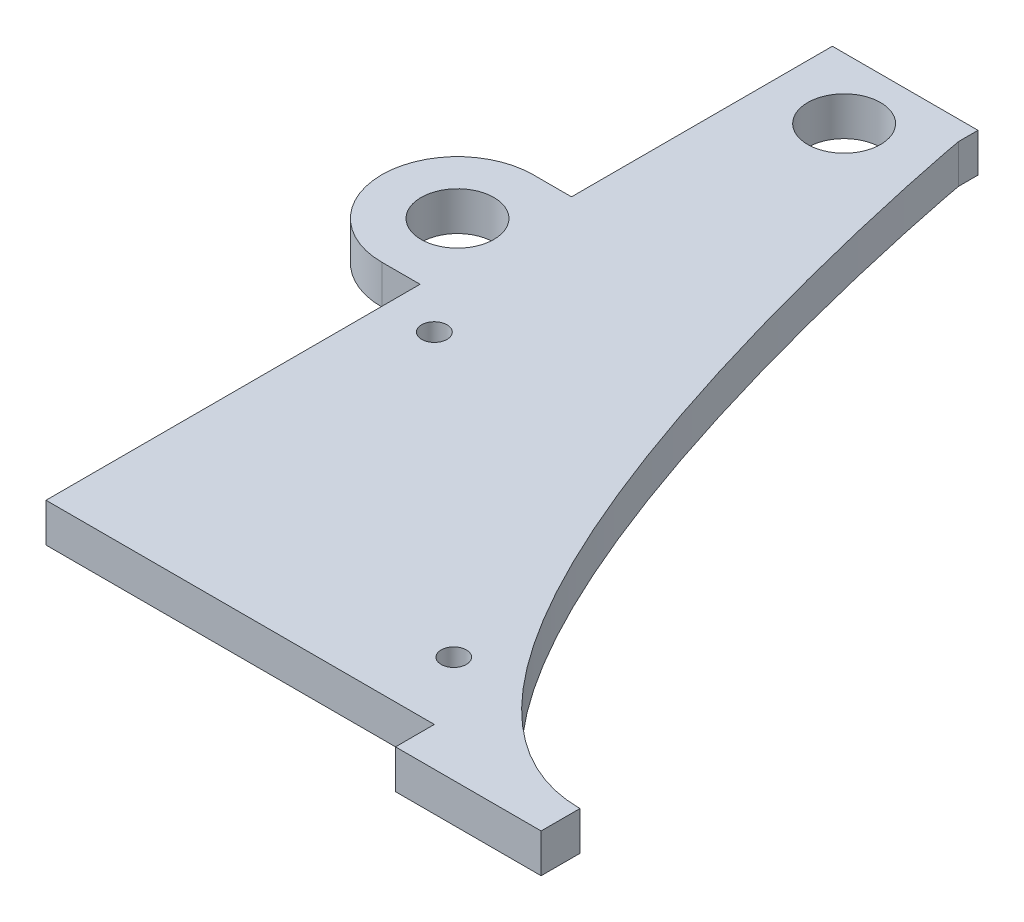
SolidWorks part; units mm, degrees
ref_plane "Front Plane" through (0, 0, 0) normal (0, 0, 1) x (1, 0, 0)
ref_plane "Top Plane" through (0, 0, 0) normal (0, 1, 0) x (1, 0, 0)
ref_plane "Right Plane" through (0, 0, 0) normal (1, 0, 0) x (0, 0, -1)
sketch "Sketch1" plane through (0, 0, 0) normal (0, 1, 0) x (1, 0, 0)
  line L0 (9.525, -53.975) -> (60.325, -53.975) construction
  line L1 (-9.525, -53.975) -> (9.525, -53.975) construction
  line L2 (-9.525, -53.975) -> (-9.525, 53.975) construction
  line L3 (-9.525, 53.975) -> (9.525, 53.975)
  line L4 (9.525, -53.975) -> (9.525, 53.975) construction
  line L5 (-9.525, -53.975) -> (9.525, 53.975) construction
  line L6 (-9.525, 53.975) -> (9.525, -53.975) construction
  line L7 (0, 53.975) -> (0, 45.9867) construction
  line L8 (-9.525, 50.7492) -> (9.525, 50.7492) construction
  line L9 (9.525, 51.435) -> (9.525, 53.975)
  line L10 (60.325, -53.975) -> (60.325, -48.895) construction
  line L11 (60.325, -48.895) -> (-9.525, -48.895) construction
  line L12 (60.325, -53.975) -> (60.325, -48.895) construction
  line L13 (60.325, -48.895) -> (-9.525, -48.895)
  line L14 (-9.525, -48.895) -> (-9.525, 53.975)
  line L15 (31.115, -19.685) -> (31.115, -48.895) construction
  circle A0 centre (0, 45.9867) radius 4.7625
  spline S0 degree 3 poles (9.525, 51.435) (9.525, 51.2145) (27.8191, -48.895) (60.325, -48.895) knots 0 0 0 0 1 1 1 1
  point P4 (0, 0)
  dimension "D5" = 9.525
  dimension "D1" = 107.95
  dimension "D2" = 19.05
  dimension "D3" = 50.8
  dimension "D4" = 2.54
  dimension "D6" = 104.7242
  dimension "D7" = 5.08
  dimension "D8" = 40.64
  dimension "D9" = 29.21
extrude "Boss-Extrude1" add sketch "Sketch1" along normal blind 5.08
sketch "Sketch4" plane through (0, 5.08, 0) normal (0, 1, 0) x (1, 0, 0)
  line L0 (-9.525, 53.975) -> (-9.525, -48.895) construction
  line L1 (60.325, -48.895) -> (41.275, -48.895)
  line L2 (60.325, -48.895) -> (60.325, -53.975)
  line L3 (60.325, -53.975) -> (41.275, -53.975)
  line L4 (41.275, -48.895) -> (41.275, -53.975)
  line L5 (60.325, -48.895) -> (41.275, -53.975) construction
  line L6 (60.325, -53.975) -> (41.275, -48.895) construction
  point P4 (50.8, -51.435)
  dimension "D1" = 50.8
  dimension "D2" = 5.08
extrude "Boss-Extrude2" add sketch "Sketch4" against normal up to surface (5.08 mm away) up to face at (17.145, 0, -2.286)
sketch "Sketch5" plane through (0, 0, 0) normal (0, -1, 0) x (1, 0, 0)
  circle A1 centre (34.925, 40.005) radius 1.651
  circle A3 centre (-3.175, 4.445) radius 1.6607
extrude "Cut-Extrude1" cut sketch "Sketch5" against normal through all both
sketch "Sketch6" plane through (0, 0, 0) normal (0, -1, 0) x (1, 0, 0)
  line L0 (-9.525, -9.9436) -> (-14.5359, -9.9436) construction
  line L1 (-9.525, -53.975) -> (-9.525, 48.895) construction
  line L2 (-14.5359, -0.0376) -> (-9.525, -0.0376)
  line L3 (-14.5359, -19.8496) -> (-9.525, -19.8496)
  line L4 (-9.525, -0.0376) -> (-9.525, -1.3984)
  line L5 (-9.525, -19.8496) -> (-9.525, -18.4887)
  line L6 (41.275, 53.975) -> (60.325, 53.975) construction
  circle A0 centre (-14.5359, -9.9436) radius 4.7625
  arc A1 (-9.525, -18.4887) -> (-9.525, -1.3984) centre (-14.5359, -9.9436) ccw
  arc A2 (-14.5359, -0.0376) -> (-14.5359, -19.8496) centre (-14.5359, -9.9436) ccw
  dimension "D1" = 63.9186
  dimension "D2" = 5.0109
extrude "Boss-Extrude3" add sketch "Sketch6" against normal blind 5.08
sketch "Sketch8" plane through (0, 5.08, 0) normal (0, 1, 0) x (1, 0, 0)
  circle A0 centre (-14.5359, 9.9436) radius 4.7625
